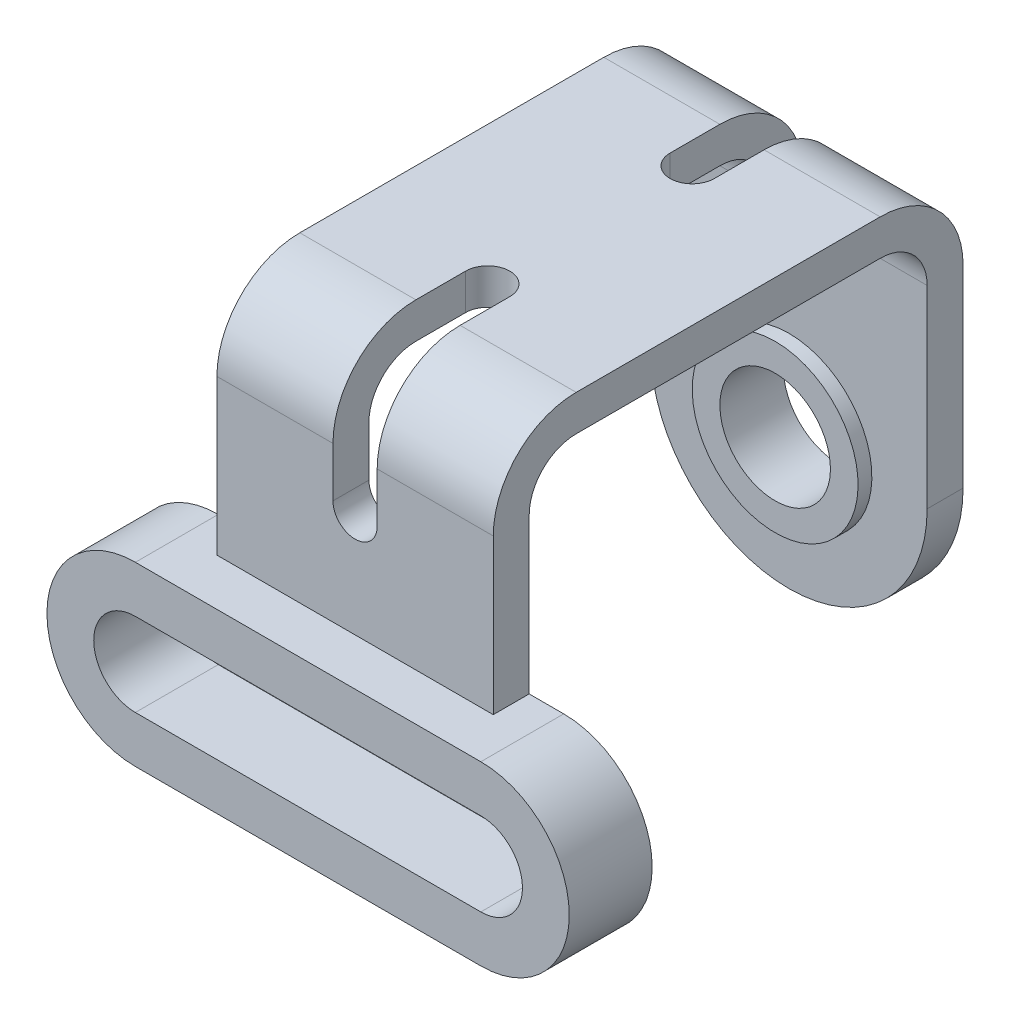
SolidWorks part; units mm, degrees
material "1345 합금"
ref_plane "정면" through (0, 0, 0) normal (0, 0, 1) x (1, 0, 0)
ref_plane "윗면" through (0, 0, 0) normal (0, 1, 0) x (1, 0, 0)
ref_plane "우측면" through (0, 0, 0) normal (1, 0, 0) x (0, 0, -1)
sketch "Sketch1" plane through (0, 0, 0) normal (1, 0, 0) x (0, 0, -1)
  line L0 (0, 0) -> (0, 137)
  line L1 (0, 137) -> (144, 137)
  line L2 (144, 137) -> (144, 0)
  line L3 (-13, 0) -> (-13, 150)
  line L4 (-13, 150) -> (157, 150)
  line L5 (157, 150) -> (157, 0)
  line L6 (0, 0) -> (-13, 0)
  line L7 (144, 0) -> (157, 0)
  dimension "D1" = 170
  dimension "D2" = 150
  dimension "D3" = 13
extrude "Boss-Extrude1" add sketch "Sketch1" along normal blind 100 contours L4 L5 L7 L2 L1 L0 L6 L3
fillet "Fillet1" radius 30 2 edges at (50, 150, -157) (50, 150, 13)
fillet "Fillet2" radius 17 2 edges at (50, 137, -144) (50, 137, 0)
sketch "Sketch2" plane through (0, 0, 13) normal (0, 0, 1) x (1, 0, 0)
  line L0 (-12.5, 32) -> (112.5, 32) construction
  line L1 (-12.5, 64) -> (112.5, 64)
  line L2 (-12.5, 0) -> (112.5, 0)
  line L3 (100, 0) -> (0, 0) construction
  line L6 (-12.5, 32) -> (112.5, 32) construction
  line L7 (-12.5, 47.0628) -> (112.5, 47.0628)
  line L8 (-12.5, 16.9372) -> (112.5, 16.9372)
  arc A0 (-12.5, 64) -> (-12.5, 0) centre (-12.5, 32) ccw
  arc A1 (112.5, 0) -> (112.5, 64) centre (112.5, 32) ccw
  arc A4 (-12.5, 47.0628) -> (-12.5, 16.9372) centre (-12.5, 32) ccw
  arc A5 (112.5, 16.9372) -> (112.5, 47.0628) centre (112.5, 32) ccw
  point P2 (50, 32)
  point P9 (50, 0)
  point P12 (50, 32)
  point P17 (0, 0)
  point P18 (50, 0)
  line M6 (100, 0) -> (100, 120)
  line M8 (0, 120) -> (0, 0)
  dimension "D1" = 64
  dimension "D2" = 125
  dimension "D3" = 30.1255
  dimension "D4" = 125
extrude "Boss-Extrude2" add sketch "Sketch2" along normal blind 17 and the other way blind 13
extrude "Cut-Extrude1" cut sketch "Sketch2<4>" against normal blind 17 contours L7 A4 L8 M8 | L8 L7 M8 M6 | L8 A5 L7 M6 region at (-12.3974, 32, 13) region at (50, 32, 13) region at (112.3974, 32, 13)
sketch "Sketch2<4>" plane through (0, 0, 13) normal (0, 0, 1) x (1, 0, 0) same geometry as "Sketch2"
fillet "Fillet3" radius 50 2 edges at (0, 0, -150.5) (100, 0, -150.5)
sketch "Sketch3" plane through (0, 0, -157) normal (0, 0, -1) x (-1, 0, 0)
  circle A0 centre (-50, 50) radius 30
  circle A1 centre (-50, 50) radius 20
  dimension "D1" = 60
  dimension "D2" = 40
extrude "Boss-Extrude3" add sketch "Sketch3" along normal blind 5 and the other way blind 18
extrude "Cut-Extrude2" cut sketch "Sketch3<2>" against normal blind 25 contours A1 region at (50, 50, -157)
sketch "Sketch3<2>" plane through (0, 0, -157) normal (0, 0, -1) x (-1, 0, 0) same geometry as "Sketch3"
sketch "Sketch4" plane through (0, 0, -157) normal (0, 0, -1) x (-1, 0, 0)
  line L0 (-50, 150) -> (-50, 102)
  line L1 (-58, 150) -> (-58, 102)
  line L2 (-42, 150) -> (-42, 102)
  arc A0 (-58, 150) -> (-42, 150) centre (-50, 150) cw
  arc A1 (-58, 102) -> (-42, 102) centre (-50, 102) ccw
  point P2 (0, 0)
  point P3 (0, 0)
  point P4 (-50, 150)
  line M10 (0, 120) -> (-100, 120)
  dimension "D2" = 8
  dimension "D1" = 48
ref_plane "Plane1" through (0, 0, -72) normal (0, 0, -1) x (-1, 0, 0)
extrude "Cut-Extrude3" cut sketch "Sketch4" against normal blind 25 contours A0 L1 L2 M10 | L1 A1 L2 M10 region at (50, 157.5877, -157) region at (54, 119.6947, -157)
sketch "Sketch5" plane through (0, 150, 0) normal (0, 1, 0) x (1, 0, 0)
  line L0 (50, 157) -> (50, 109) construction
  line L1 (58, 157) -> (42, 157) construction
  line L2 (58, 157) -> (58, 109)
  line L3 (42, 157) -> (42, 109)
  line L4 (50, -13) -> (50, 35) construction
  line L5 (100, -13) -> (0, -13) construction
  line L6 (42, -13) -> (42, 35)
  line L7 (58, -13) -> (58, 35)
  arc A0 (58, 157) -> (42, 157) centre (50, 157) ccw
  arc A1 (42, 109) -> (58, 109) centre (50, 109) ccw
  arc A2 (42, -13) -> (58, -13) centre (50, -13) ccw
  arc A3 (58, 35) -> (42, 35) centre (50, 35) ccw
  point P4 (50, 133)
  point P9 (50, 11)
  dimension "D3" = 8
  dimension "D4" = 8
  dimension "D1" = 48
  dimension "D2" = 48
extrude "Cut-Extrude4" cut sketch "Sketch5" against normal blind 25
sketch "Sketch6" plane through (0, 0, 13) normal (0, 0, 1) x (1, 0, 0)
  line L0 (50, 150) -> (50, 102) construction
  line L1 (58, 150) -> (42, 150) construction
  line L2 (58, 150) -> (58, 102)
  line L3 (42, 150) -> (42, 102)
  arc A0 (58, 150) -> (42, 150) centre (50, 150) ccw
  arc A1 (42, 102) -> (58, 102) centre (50, 102) ccw
  point P4 (50, 126)
  dimension "D1" = 8
  dimension "D2" = 48
extrude "Cut-Extrude5" cut sketch "Sketch6" against normal blind 25
